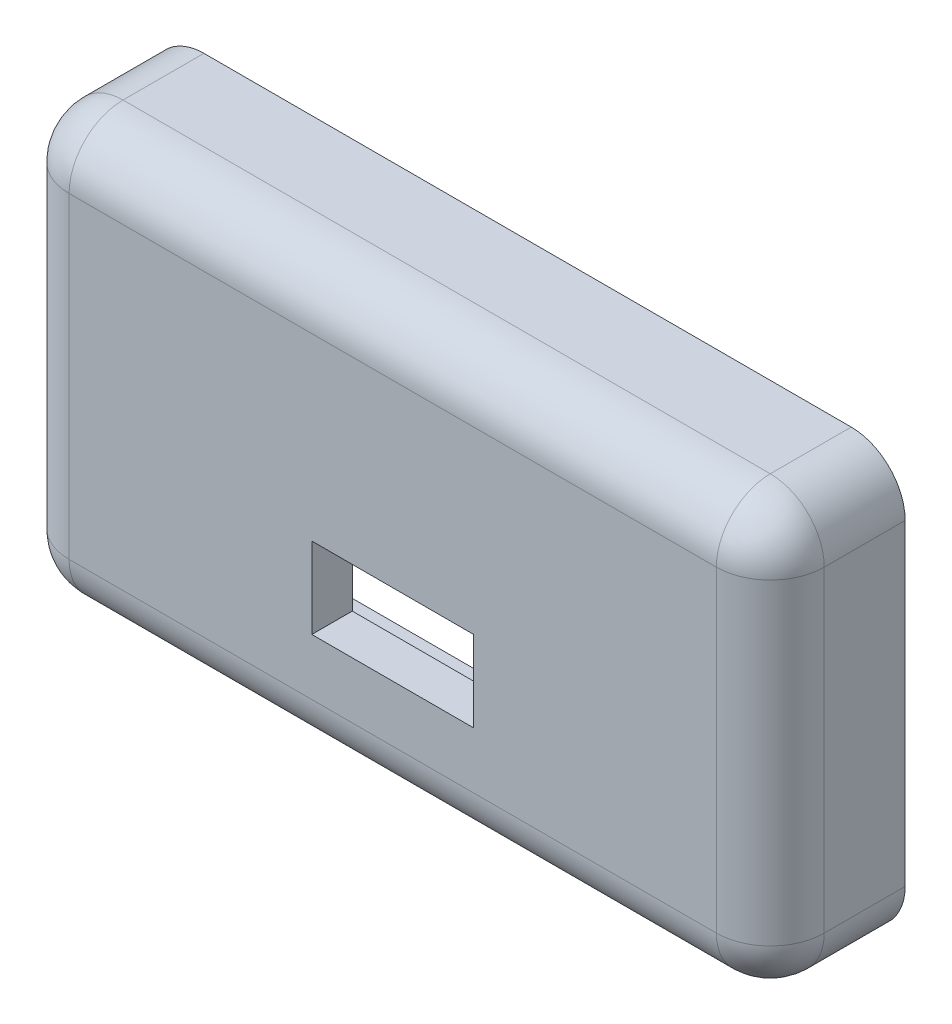
SolidWorks part; units mm, degrees
ref_plane "Přední rovina" through (0, 0, 0) normal (0, 0, 1) x (1, 0, 0)
ref_plane "Horní rovina" through (0, 0, 0) normal (0, 1, 0) x (1, 0, 0)
ref_plane "Pravá rovina" through (0, 0, 0) normal (1, 0, 0) x (0, 0, -1)
sketch "Sketch1" plane through (0, 0, 0) normal (0, 0, 1) x (1, 0, 0)
  line L1 (-14, 7.875) -> (14, 7.875)
  line L2 (-14, 7.875) -> (-14, -7.875)
  line L3 (-14, -7.875) -> (14, -7.875)
  line L4 (14, 7.875) -> (14, -7.875)
  line L5 (-14, 7.875) -> (14, -7.875) construction
  line L6 (-14, -7.875) -> (14, 7.875) construction
  line L7 (-3, -0.785) -> (3, -0.785)
  line L8 (-3, -0.785) -> (-3, -3.785)
  line L9 (-3, -3.785) -> (3, -3.785)
  line L10 (3, -0.785) -> (3, -3.785)
  line L11 (-3, -0.785) -> (3, -3.785) construction
  line L12 (-3, -3.785) -> (3, -0.785) construction
  point P0 (0, 0)
  point P6 (0, -2.285)
  point P11 (0, 0)
  dimension "D1" = 28
  dimension "D2" = 15.75
  dimension "D3" = 6
  dimension "D4" = 3
  dimension "D5" = 5.59
extrude "Boss-Extrude1" add sketch "Sketch1" along normal blind 1
sketch "Sketch2" plane through (0, 0, 1) normal (0, 0, 1) x (1, 0, 0)
  line L0 (-10, 0) -> (10, 0) construction
  circle A0 centre (10, 0) radius 1.475
  circle A1 centre (-10, 0) radius 1.475
  dimension "D1" = 2.95
  dimension "D2" = 2.95
  dimension "D3" = 20
extrude "Cut-Extrude1" cut sketch "Sketch2" against normal up to next
sketch "Sketch5" plane through (0, 0, 1) normal (0, 0, 1) x (1, 0, 0)
  line L0 (3, -3.785) -> (3, -0.785) construction
  line L1 (-3, -3.785) -> (3, -3.785) construction
  line L2 (-3, -0.785) -> (-3, -3.785) construction
  line L3 (3, -0.785) -> (-3, -0.785) construction
  line L4 (14, -7.875) -> (14, 7.875)
  line L5 (14, 7.875) -> (-14, 7.875)
  line L6 (-14, 7.875) -> (-14, -7.875)
  line L7 (-14, -7.875) -> (14, -7.875)
  line L8 (14, -7.875) -> (14, 7.875)
  line L9 (14, 7.875) -> (-14, 7.875)
  line L10 (-14, 7.875) -> (-14, -7.875)
  line L11 (-14, -7.875) -> (14, -7.875)
  line L12 (3, -3.785) -> (3, -0.785)
  line L13 (-3, -3.785) -> (3, -3.785)
  line L14 (-3, -0.785) -> (-3, -3.785)
  line L15 (3, -0.785) -> (-3, -0.785)
  dimension "D1" = 0
extrude "Boss-Extrude4" add sketch "Sketch5" along normal blind 0.5
sketch "Sketch3" plane through (0, 0, 0) normal (0, 0, -1) x (-1, 0, 0)
  circle A0 centre (-10, 0) radius 1.475
  circle A1 centre (10, 0) radius 1.475
  circle A2 centre (-10, 0) radius 1.475 construction
  circle A3 centre (10, 0) radius 1.475 construction
  circle A4 centre (-10, 0) radius 2.475
  circle A5 centre (10, 0) radius 2.475
  dimension "D1" = 1
  dimension "D2" = 1
extrude "Boss-Extrude2" add sketch "Sketch3" along normal blind 1
sketch "Sketch4" plane through (0, 0, 0) normal (0, 0, -1) x (-1, 0, 0)
  line L1 (-13, -6.875) -> (13, -6.875)
  line L2 (-13, -6.875) -> (-13, 6.875)
  line L3 (-13, 6.875) -> (13, 6.875)
  line L4 (-14, 7.875) -> (-14, -7.875)
  line L5 (-14, -7.875) -> (14, -7.875)
  line L6 (14, -7.875) -> (14, 7.875)
  line L7 (14, 7.875) -> (-14, 7.875)
  line L8 (-14, 7.875) -> (-14, -7.875)
  line L9 (-14, -7.875) -> (14, -7.875)
  line L10 (14, -7.875) -> (14, 7.875)
  line L11 (14, 7.875) -> (-14, 7.875)
  line L12 (13, -6.875) -> (13, 6.875)
  line L13 (-13, -6.875) -> (13, 6.875) construction
  line L14 (-13, 6.875) -> (13, -6.875) construction
  point P2 (0, 0)
  dimension "D2" = 1
  dimension "D3" = 1
  dimension "D1" = 0
extrude "Boss-Extrude3" add sketch "Sketch4" along normal blind 3.5
fillet "Fillet1" radius 2 8 edges at (14, 7.875, -1) (14, -7.875, -1) (-14, -7.875, -1) (-14, 7.875, -1) (0, -7.875, 1.5) (14, 0, 1.5) (0, 7.875, 1.5) (-14, 0, 1.5)
